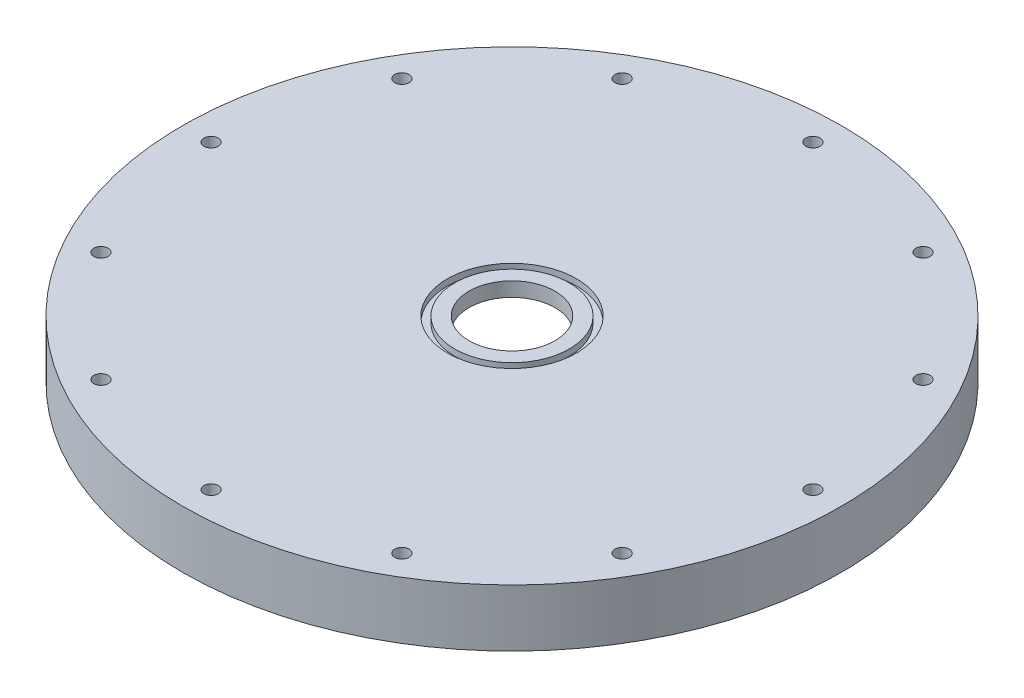
SolidWorks part; units mm, degrees
ref_plane "Front Plane" through (0, 0, 0) normal (0, 0, 1) x (1, 0, 0)
ref_plane "Top Plane" through (0, 0, 0) normal (0, 1, 0) x (1, 0, 0)
ref_plane "Right Plane" through (0, 0, 0) normal (1, 0, 0) x (0, 0, -1)
sketch "Sketch1" plane through (0, 0, 0) normal (0, 0, 1) x (1, 0, 0)
  line L0 (0, 0) -> (0, 6.35)
  line L1 (0, 6.35) -> (-146.05, 6.35)
  line L2 (-146.05, 6.35) -> (-146.05, -19.05)
  line L3 (-146.05, -19.05) -> (-112.522, -19.05)
  line L4 (-112.522, -19.05) -> (-112.522, -16.51)
  line L5 (-96.012, 0) -> (0, 0)
  arc A0 (-112.522, -16.51) -> (-96.012, 0) centre (-96.012, -16.51) cw
  dimension "D5" = 16.51
  dimension "D1" = 146.05
  dimension "D2" = 6.35
  dimension "D3" = 25.4
  dimension "D4" = 33.528
revolve "Revolve1" add sketch "Sketch1" angle 360 about L0
sketch "Sketch2" plane through (0, 6.35, 0) normal (0, 1, 0) x (1, 0, 0)
  circle A0 centre (0, 0) radius 19.05
extrude "Cut-Extrude1" cut sketch "Sketch2" against normal through all
sketch "Sketch3" plane through (0, 6.35, 0) normal (0, 1, 0) x (1, 0, 0)
  circle A0 centre (0, 0) radius 25.4
  circle A1 centre (0, 0) radius 28.575
  dimension "D1" = 57.15
  dimension "D2" = 50.8
extrude "Cut-Extrude2" cut sketch "Sketch3" against normal blind 2.794
sketch "Sketch4" plane through (0, 6.35, 0) normal (0, 1, 0) x (1, 0, 0)
  point P0 (0, 133.35)
  point P5 (66.675, 115.4845)
  point P6 (115.4845, 66.675)
  point P7 (133.35, 0)
  point P8 (115.4845, -66.675)
  point P9 (66.675, -115.4845)
  point P10 (0, -133.35)
  point P11 (-66.675, -115.4845)
  point P12 (-115.4845, -66.675)
  point P13 (-133.35, 0)
  point P14 (-115.4845, 66.675)
  point P15 (-66.675, 115.4845)
  point P16 (0, 0)
  dimension "D1" = 133.35
  dimension "D2" = 12
hole_wizard "1/4 (0.25) Diameter Hole1" positions "3DSketch1" profile "Sketch5" hole size "1/4" standard "ANSI Inch" end condition through all
sketch3d "3DSketch1"
  point P0 (0, 6.35, -133.35)
  point P3 (-66.675, 6.35, -115.4845)
  point P6 (-115.4845, 6.35, -66.675)
  point P9 (-133.35, 6.35, 0)
  point P12 (-115.4845, 6.35, 66.675)
  point P15 (-66.675, 6.35, 115.4845)
  point P18 (0, 6.35, 133.35)
  point P21 (66.675, 6.35, 115.4845)
  point P24 (115.4845, 6.35, 66.675)
  point P27 (133.35, 6.35, 0)
  point P30 (115.4845, 6.35, -66.675)
  point P33 (66.675, 6.35, -115.4845)
sketch "Sketch5" plane through (0, 6.35, -133.35) normal (1, 0, 0) x (0, 0, 1)
  line L0 (0, 0) -> (0, 25.4)
  line L1 (0, 25.4) -> (3.175, 25.4)
  line L2 (3.175, 25.4) -> (3.175, 0)
  line L5 (3.175, 0) -> (0, 0)
  line L11 (0, -6.35) -> (0, 107.95) construction
  dimension "Thru Hole Dia." = 6.35
  dimension "Thru Hole Depth" = 25.4
